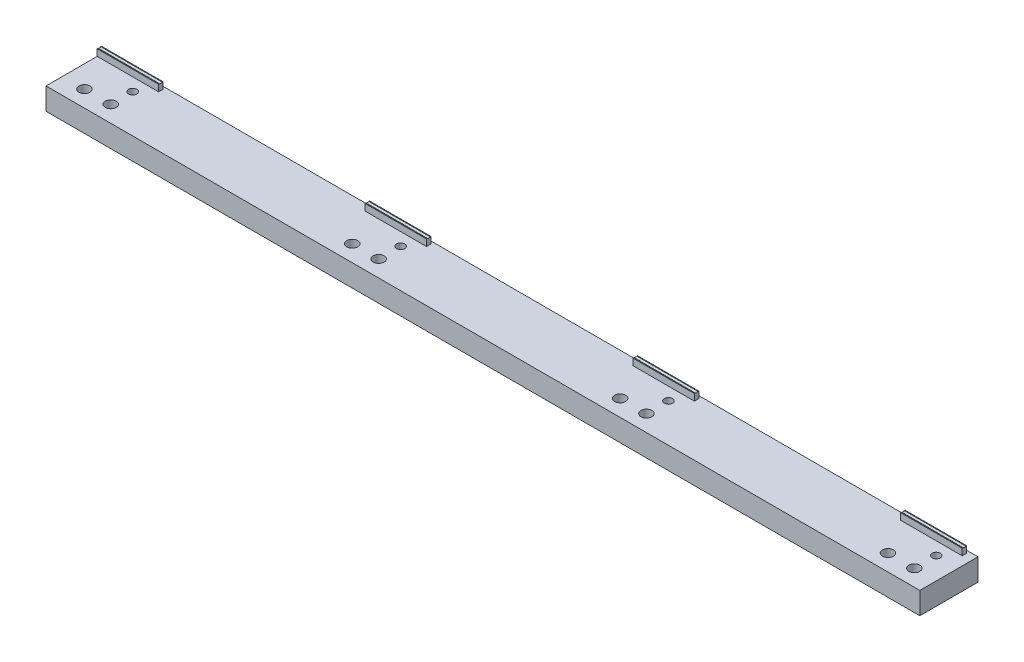
SolidWorks part; units mm, degrees
ref_plane "Front Plane" through (0, 0, 0) normal (0, 0, 1) x (1, 0, 0)
ref_plane "Top Plane" through (0, 0, 0) normal (0, 1, 0) x (1, 0, 0)
ref_plane "Right Plane" through (0, 0, 0) normal (1, 0, 0) x (0, 0, -1)
sketch "Sketch2" plane through (0, 0, 0) normal (0, 1, 0) x (1, 0, 0)
  line L0 (0, 15) -> (796, 15) construction
  line L1 (0, 0) -> (796, 0)
  line L2 (0, 0) -> (0, 53)
  line L3 (0, 53) -> (796, 53)
  line L4 (796, 0) -> (796, 53)
  line L6 (752, 53) -> (752, 0) construction
  line L11 (0, 35) -> (796, 35) construction
  line L12 (776, 53) -> (776, 0) construction
  circle A5 centre (752, 15) radius 5
  circle A9 centre (776, 35) radius 3.75
  circle A10 centre (776, 15) radius 5
  dimension "D6" = 10
  dimension "D12" = 7.5
  dimension "D1" = 796
  dimension "D2" = 53
  dimension "D7" = 15
  dimension "D10" = 20
  dimension "D11" = 24
  dimension "D13" = 20
extrude "Boss-Extrude1" add sketch "Sketch2" along normal blind 20 contours L1 L4 L3 L2 A10 A9 A5 | A5 | A10 | A9 region at (396.233, 0, -26.5341) region at (752, 0, -15) region at (776, 0, -35) region at (776, 0, -15)
extrude "Cut-Extrude1" cut sketch "Sketch2<3>" along normal through all both and the other way through all contours A5 | A10 | A9 region at (752, 0, -15) region at (776, 0, -35) region at (776, 0, -15)
sketch "Sketch2<3>" plane through (0, 0, 0) normal (0, 1, 0) x (1, 0, 0) same geometry as "Sketch2"
sketch "Sketch3" plane through (796, 0, 0) normal (1, 0, 0) x (0, 0, -1)
  line L0 (0, 20) -> (53, 20) construction
  line L1 (50.625, 20) -> (46.625, 20)
  line L2 (50.625, 20) -> (50.625, 26)
  line L3 (50.625, 26) -> (49.9059, 26)
  line L4 (46.625, 20) -> (46.625, 26)
  line L5 (53, 20) -> (53, 0) construction
  line L6 (48.625, 20) -> (48.625, 28) construction
  line L7 (49.9059, 26) -> (48.625, 26) construction
  line L8 (47.3441, 26) -> (46.625, 26)
  line L9 (48.625, 26) -> (47.3441, 26) construction
  arc A0 (47.3441, 26) -> (49.9059, 26) centre (48.625, 28) ccw
  arc A1 (49.9059, 26) -> (47.3441, 26) centre (48.625, 28) ccw construction
  dimension "D5" = 4.75
  dimension "D1" = 2.375
  dimension "D2" = 4
  dimension "D3" = 6
  dimension "D4" = 2
extrude "Boss-Extrude2" add sketch "Sketch3" against normal blind 56 from offset 8 offset against normal yes
pattern_linear "LPattern1" count 4 spacing 244 along (-1, 0, 0) of "Cut-Extrude1", "Boss-Extrude2"
